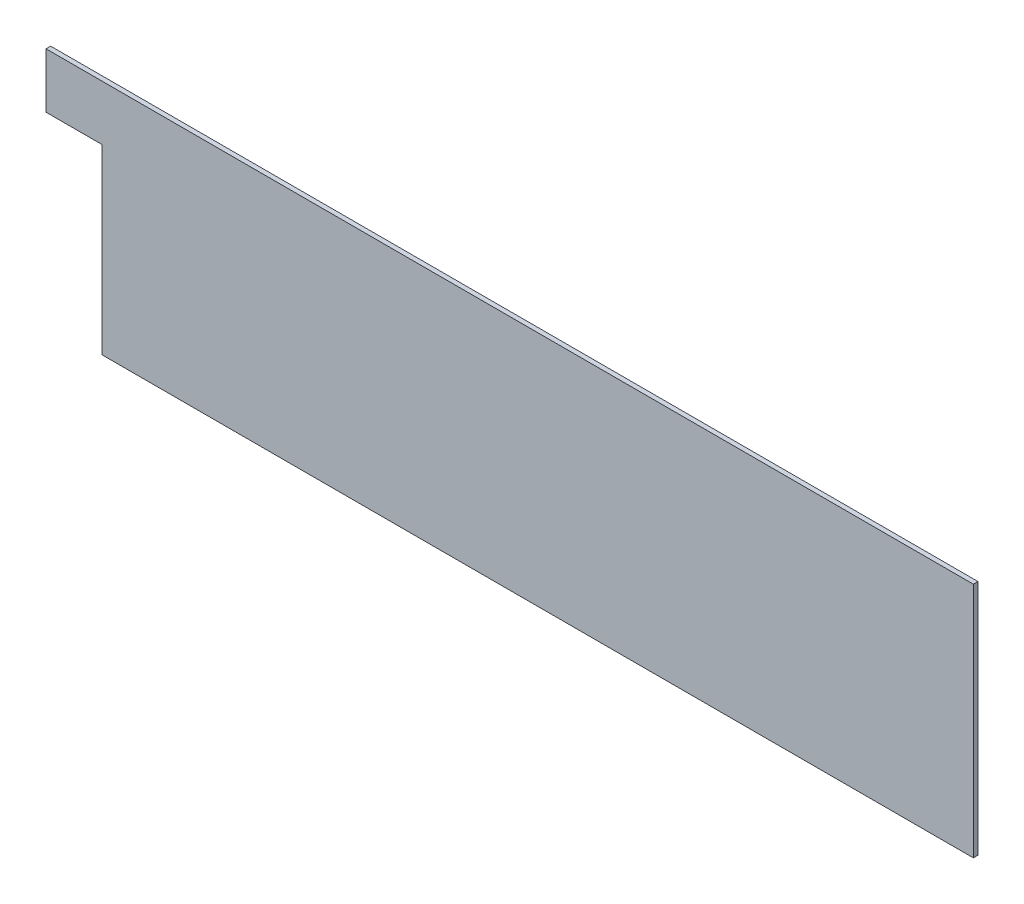
SolidWorks part; units mm, degrees
ref_plane "Ön Düzlem" through (0, 0, 0) normal (0, 0, 1) x (1, 0, 0)
ref_plane "Üst Düzlem" through (0, 0, 0) normal (0, 1, 0) x (1, 0, 0)
ref_plane "Sağ Düzlem" through (0, 0, 0) normal (1, 0, 0) x (0, 0, -1)
sketch "Çizim1" plane through (0, 0, 0) normal (0, 0, 1) x (1, 0, 0)
  line L0 (0, 0) -> (0, -1015)
  line L1 (0, -1015) -> (365, -1015)
  line L2 (365, -1015) -> (365, -1540)
  line L3 (365, -1540) -> (6025, -1540)
  line L4 (6025, -1540) -> (6025, 0)
  line L5 (6025, 0) -> (0, 0)
  dimension "D1" = 1015
  dimension "D2" = 365
  dimension "D3" = 525
  dimension "D4" = 5660
  dimension "D5" = 1540
  dimension "D6" = 6025
base flange "Taban-Flanş1" sketch "Çizim1" thickness 30 reverse thickness direction no parameters "D1"=8
sketch "Çizim2" plane through (0, 0, 0) normal (0, 0, 1) x (1, 0, 0)
  line L0 (0, 0) -> (0, -1015) construction
  line L1 (365, -1015) -> (0, -1015)
  line L2 (365, -1015) -> (365, -357)
  line L3 (365, -357) -> (0, -357)
  line L4 (0, -1015) -> (0, -357)
  line L5 (6025, 0) -> (0, 0) construction
  dimension "D1" = 357
extrude "Kes-Ekstrüzyon1" cut sketch "Çizim2" against normal through all both and the other way through all
sketch "Büküm-Çizgileri1" [suppressed] plane through (0, 0, 0) normal (0, 1, 0) x (1, 0, 0)
sketch "Sınırlandırma-Kutusu1" [suppressed] plane through (0, 0, 0) normal (0, 1, 0) x (1, 0, 0)
sheet metal parameters "Sac-Levha1" thickness 30 parameters "D1"=8
flat pattern "Düz-Çoğaltma1" [suppressed]
sketch "Büküm-Çizgileri2" plane through (0, 0, 0) normal (0, 1, 0) x (1, 0, 0)
sketch3d "Sınırlandırma-Kutusu2" [suppressed]
  line L0 (0, -1540, 0) -> (6025, -1540, 0) construction
  line L1 (0, 0, 0) -> (6025, 0, 0) construction
  line L2 (0, -1540, 0) -> (0, 0, 0) construction
  line L3 (6025, -1540, 0) -> (6025, 0, 0) construction
sheet metal parameters "Sac-Levha2" thickness 30 parameters "D1"=8
flat pattern "Düz-Çoğaltma1"
sketch "Büküm-Çizgileri2" plane through (0, 0, 0) normal (0, 1, 0) x (1, 0, 0)
sketch3d "Sınırlandırma-Kutusu2" [suppressed]
  line L0 (0, -1540, 0) -> (6025, -1540, 0) construction
  line L1 (0, 0, 0) -> (6025, 0, 0) construction
  line L2 (0, -1540, 0) -> (0, 0, 0) construction
  line L3 (6025, -1540, 0) -> (6025, 0, 0) construction
